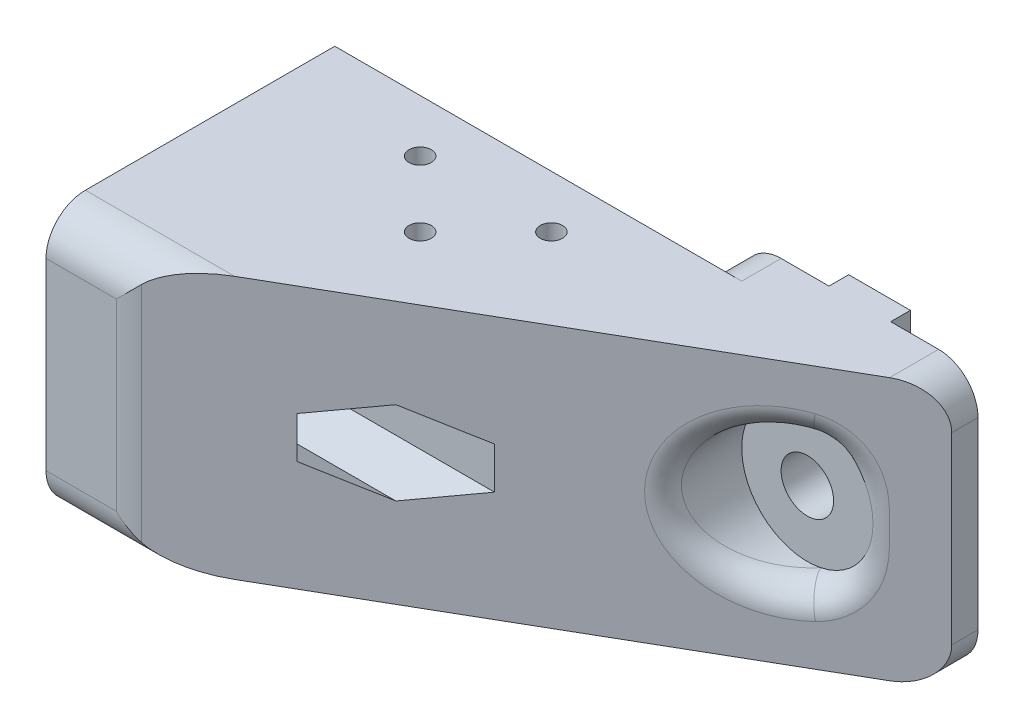
SolidWorks part; units mm, degrees
material "ABS"
ref_plane "Plan de face" through (0, 0, 0) normal (0, 0, 1) x (1, 0, 0)
ref_plane "Plan de dessus" through (0, 0, 0) normal (0, 1, 0) x (1, 0, 0)
ref_plane "Plan de droite" through (0, 0, 0) normal (1, 0, 0) x (0, 0, -1)
sketch "Esquisse1" plane through (0, 0, 0) normal (0, 1, 0) x (1, 0, 0)
  line L0 (2.35, 0) -> (9, 0)
  line L1 (-2.35, 1.5) -> (2.35, 1.5)
  line L2 (-2.35, 1.5) -> (-2.35, 0)
  line L3 (-2.35, 0) -> (2.35, 0) construction
  line L4 (2.35, 1.5) -> (2.35, 0)
  line L5 (-9, 0) -> (-2.35, 0)
  line L6 (-9, 0) -> (-9, -3)
  line L7 (-30.8372, -25) -> (-37, -25)
  line L8 (9, -2) -> (-30.8372, -25)
  line L10 (9, -2) -> (9, 0)
  line L13 (-37, -25) -> (-37, -3)
  line L14 (-37, -3) -> (-9, -3)
  circle A0 centre (-26.5, -7) radius 0.85
  circle A1 centre (-16.5, -7) radius 0.85
  circle A2 centre (-21.5, -12) radius 0.85
  dimension "D10" = 10
  dimension "D11" = 4
  dimension "D12" = 16.5
  dimension "D13" = 1.7
  dimension "D7" = 5
  dimension "D14" = 5
  dimension "D1" = 9
  dimension "D2" = 25
  dimension "D3" = 2
  dimension "D4" = 4.7
  dimension "D5" = 1.5
  dimension "D6" = 30
  dimension "D8" = 37
  dimension "D9" = 3
extrude "Boss.-Extru.1" add sketch "Esquisse1" along normal mid plane 20
sketch "Esquisse2" plane through (-1.3724, 0, 0) normal (0, 0, 1) x (1, 0, 0)
  circle A0 centre (1.3724, 0) radius 2
  dimension "D1" = 4
extrude "Enlèv. mat.-Extru.1" cut sketch "Esquisse2" against normal through all both and the other way through all
sketch "Esquisse3" plane through (0, 0, 0) normal (0, 0, 1) x (1, 0, 0)
  circle A0 centre (0, 0) radius 5
  dimension "D1" = 10
extrude "Enlèv. mat.-Extru.2" cut sketch "Esquisse3" along normal through all draft 2 from offset 4
fillet "Congé1" radius 3 7 edges at (-9, -10, 1.5) (-9, 10, 1.5) (9, -10, 1) (9, 10, 1) (-33.9186, -10, 25) (-33.9186, 10, 25) (-30.8372, 0, 25)
fillet "Congé2" radius 2 1 edges at (4.989, 0, 4.3158)
sketch "Esquisse4" plane through (-37, 0, 0) normal (-1, 0, 0) x (0, 0, 1)
  circle A0 centre (17.5, 0) radius 1.5
  dimension "D1" = 17.5
  dimension "D2" = 3
extrude "Enlèv. mat.-Extru.3" cut sketch "Esquisse4" against normal through all
sketch "Esquisse5" plane through (-37, 0, 0) normal (-1, 0, 0) x (0, 0, 1)
  line L1 (20.25, 1.5877) -> (17.5, 3.1754)
  line L2 (17.5, 3.1754) -> (14.75, 1.5877)
  line L3 (14.75, 1.5877) -> (14.75, -1.5877)
  line L4 (14.75, -1.5877) -> (17.5, -3.1754)
  line L5 (17.5, -3.1754) -> (20.25, -1.5877)
  line L6 (20.25, -1.5877) -> (20.25, 1.5877)
  circle A0 centre (17.5, 0) radius 2.75 construction
  dimension "D1" = 5.5
extrude "Enlèv. mat.-Extru.4" cut sketch "Esquisse5" against normal through all from offset 3 offset against normal yes
sketch "Esquisse6" plane through (0, -10, 0) normal (0, -1, 0) x (1, 0, 0)
  line L11 (6, 3.7321) -> (-25.641, 22)
  line L12 (-25.641, 22) -> (-37, 22)
  line L13 (-37, 22) -> (-37, 3)
  line L14 (-37, 3) -> (-6, 3)
  line L15 (-6, 3) -> (-6, 0)
  line L16 (-6, 0) -> (-2.35, 0)
  line L17 (-2.35, 0) -> (-2.35, -1.5)
  line L18 (-2.35, -1.5) -> (2.35, -1.5)
  line L19 (2.35, -1.5) -> (2.35, 0)
  line L20 (2.35, 0) -> (6, 0)
  line L21 (6, 0) -> (6, 3.7321)
  line L22 (6, 3.7321) -> (-25.641, 22)
  line L23 (-25.641, 22) -> (-37, 22)
  line L24 (-37, 22) -> (-37, 3)
  line L25 (-37, 3) -> (-6, 3)
  line L26 (-6, 3) -> (-6, 0)
  line L27 (-6, 0) -> (-2.35, 0)
  line L28 (-2.35, 0) -> (-2.35, -1.5)
  line L29 (-2.35, -1.5) -> (2.35, -1.5)
  line L30 (2.35, -1.5) -> (2.35, 0)
  line L31 (2.35, 0) -> (6, 0)
  line L32 (6, 0) -> (6, 3.7321)
  dimension "D1" = 0
extrude "Boss.-Extru.2" [suppressed] add sketch "Esquisse6" against normal blind 0.2
